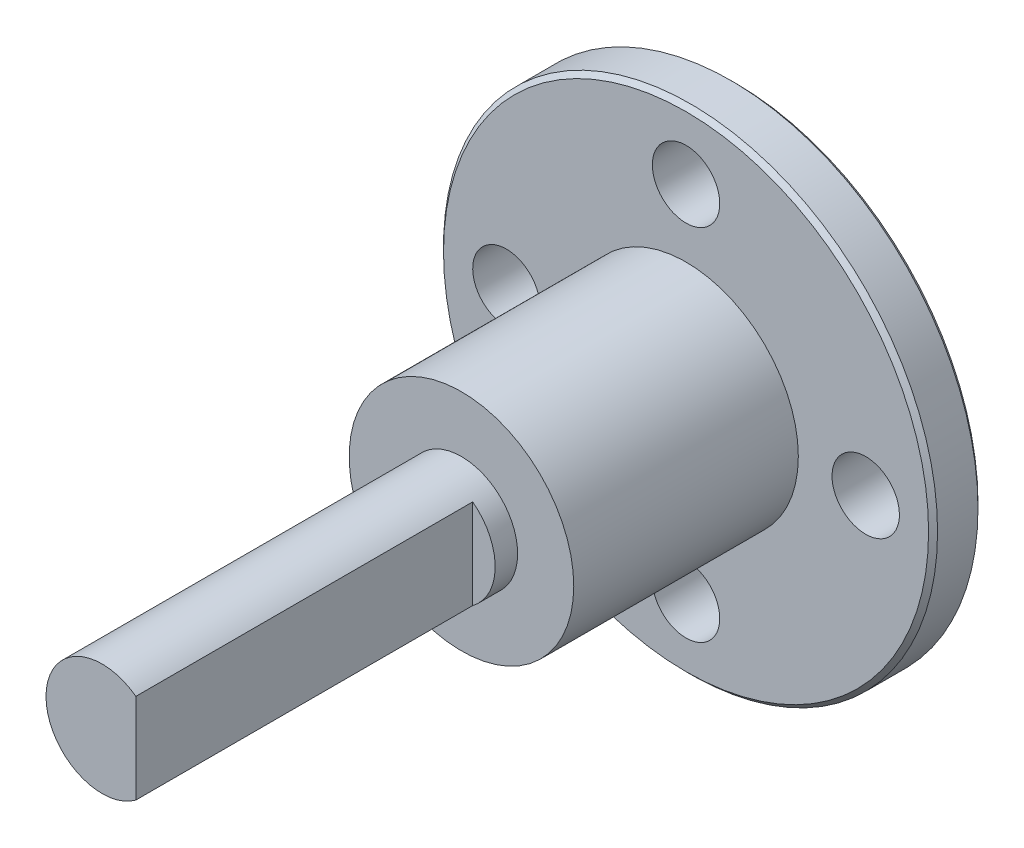
SolidWorks part; units mm, degrees
material "AISI 304"
ref_plane "前视基准面" through (0, 0, 0) normal (0, 0, 1) x (1, 0, 0)
ref_plane "上视基准面" through (0, 0, 0) normal (0, 1, 0) x (1, 0, 0)
ref_plane "右视基准面" through (0, 0, 0) normal (1, 0, 0) x (0, 0, -1)
sketch "草图1" plane through (0, 0, 0) normal (0, 0, 1) x (1, 0, 0)
  circle A3 centre (0, 0) radius 5
  circle A4 centre (0, 0) radius 11
  point P7 (0, 0)
  dimension "D1" = 22
  dimension "D2" = 10
extrude "凸台-拉伸1" add sketch "草图1" along normal blind 2.2 contours A3 | A4 A3 region at (0, 0, 0) region at (-10.6889, 0, 0)
sketch "草图2" plane through (0, 0, 2.2) normal (0, 0, 1) x (1, 0, 0)
  circle A0 centre (0, 0) radius 5
  dimension "D1" = 10
extrude "凸台-拉伸2" add sketch "草图2" along normal blind 10
hole_wizard "Ø3.0mm 暗销孔1" positions "草图8" profile "草图9" hole size "Ø3.0" standard "GB" end condition through all
sketch "草图8" plane through (0, 0, 2.2) normal (0, 0, 1) x (1, 0, 0)
  line L0 (0, 0) -> (0, 8) construction
  point P0 (0, 8)
  dimension "D1" = 8
sketch "草图9" plane through (0, 8, 2.2) normal (1, 0, 0) x (0, -1, 0)
  line L0 (0, 0) -> (0, 2.2)
  line L1 (0, 2.2) -> (1.5, 2.2)
  line L2 (1.5, 2.2) -> (1.5, 0)
  line L5 (1.5, 0) -> (0, 0)
  line L11 (0, -6.35) -> (0, 107.95) construction
  dimension "通孔孔直径" = 3
  dimension "通孔孔深度" = 2.2
pattern_circular "阵列(圆周)1" count 4 over 360 about axis through (0, 0, 2.2) along (0, 0, -1) of "Ø3.0mm 暗销孔1"
chamfer "倒角3" distance 0.2 angle 45 2 edges at (11, 0, 0) (11, 0, 2.2)
sketch "草图12" plane through (0, 0, 2.2) normal (0, 0, 1) x (1, 0, 0)
  circle A0 centre (0, 0) radius 2.5
  dimension "D1" = 5
extrude "轴" add sketch "草图12" along normal blind 26
sketch "草图13" plane through (0, 0, 28.2) normal (0, 0, 1) x (1, 0, 0)
  line L0 (0, 0) -> (4.1196, 0) construction
  line L1 (1.5, 2.6158) -> (1.5, -2.6158)
  circle A0 centre (0, 0) radius 2.5 construction
  circle A1 centre (0, 0) radius 2.5
  point P6 (1.5, 0)
  circle M2 centre (0, 0) radius 2.5
  dimension "D1" = 1.5
extrude "切除-拉伸1" cut sketch "草图13" against normal blind 15 contours L0 L1 M2 | L1 L0 A1 region at (1.9078, 0.775, 28.2) region at (1.9078, -0.775, 28.2)
